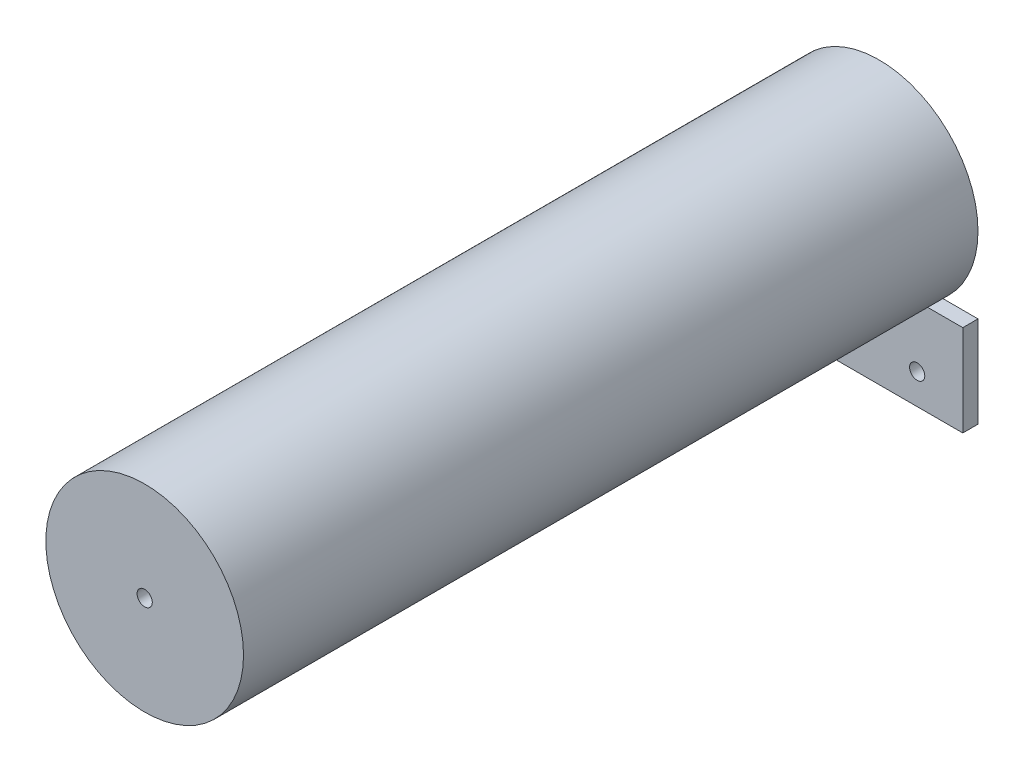
SolidWorks part; units mm, degrees
other "Asse"
other "PiastrinaAsse"
ref_plane "Piano frontale" through (0, 0, 0) normal (0, 0, 1) x (1, 0, 0)
ref_plane "Piano superiore" through (0, 0, 0) normal (0, 1, 0) x (1, 0, 0)
ref_plane "Piano destro" through (0, 0, 0) normal (1, 0, 0) x (0, 0, -1)
sketch "Sketch1" plane through (0, 0, 0) normal (0, 0, 1) x (1, 0, 0)
  circle A0 centre (0, 0) radius 65
  dimension "D1" = 130
extrude "ExtrudeAsse" add sketch "Sketch1" along normal blind 468 and the other way blind 15 contours A0 region at (0, 0, 0)
sketch "Sketch2" plane through (0, 0, 0) normal (0, 1, 0) x (1, 0, 0)
  line L0 (0, 0) -> (0, -468) construction
  line L1 (-65, -468) -> (65, -468) construction
  line L2 (65, -226.5) -> (-65, -226.5) construction
  line L3 (65, -468) -> (65, 15) construction
  line L4 (-65, 15) -> (-65, -468) construction
sketch "Sketch3" plane through (0, 0, 0) normal (1, 0, 0) x (0, 0, -1)
  line L0 (-468, 0) -> (0, 0) construction
  line L1 (-468, 65) -> (-468, -65) construction
  line L2 (-457.533, 10) -> (-194.4071, 10) construction
  line L4 (-335.5, 10) -> (-340.5, 12.8868)
  line L5 (-340.5, 12.8868) -> (-340.5, 10)
  line L7 (-227.7, 10) -> (-232.7, 12.8868)
  line L8 (-232.7, 12.8868) -> (-232.7, 0)
  line L9 (-340.5, 10) -> (-340.5, -65)
  line L10 (-468, -65) -> (15, -65) construction
  line L11 (-340.5, -65) -> (-335.5, -65)
  line L12 (-335.5, -65) -> (-335.5, 10)
  line L13 (-232.7, 0) -> (-232.7, -65)
  line L14 (-232.7, -65) -> (-227.7, -65)
  line L15 (-227.7, -65) -> (-227.7, 10)
  line L21 (-124.9, 10) -> (-124.9, 12.8868)
  line L22 (-124.9, 12.8868) -> (-119.9, 10)
  line L23 (-119.9, 10) -> (-119.9, -65)
  line L24 (-119.9, -65) -> (-124.9, -65)
  line L25 (-124.9, -65) -> (-124.9, 10)
  line L26 (-453, 40.9604) -> (-453, -28.8955) construction
  line L27 (-340.5, 12.8868) -> (-232.7, 12.8868) construction
  line L28 (-232.7, 12.8868) -> (-124.9, 12.8868) construction
  point P10 (-335.5, 9.1219)
  dimension "D1" = 10
  dimension "D2" = 5
  dimension "D3" = 124.9
  dimension "D4" = 30
  dimension "D5" = 5
  dimension "D6" = 5
  dimension "D7" = 107.8
  dimension "D8" = 30
  dimension "D10" = 15
  dimension "D11" = 30
revolve "Cut-Revolve1" cut sketch "Sketch3" angle 360 about L5 region at (0, -26.7738, 338.0157)
revolve "Cut-Revolve2" cut sketch "Sketch3<3>" angle 360 about L13 region at (0, -26.7738, 230.2157)
sketch "Sketch3<3>" plane through (0, 0, 0) normal (1, 0, 0) x (0, 0, -1) same geometry as "Sketch3"
sketch "Sketch4" plane through (0, 0, 0) normal (1, 0, 0) x (0, 0, -1)
  line L0 (-468, 0) -> (98.5282, 0) construction
  line L1 (-468, 65) -> (-468, -65) construction
  line L7 (-197.7711, -5) -> (-468, -5)
  line L8 (-468, -5) -> (-468, 0)
  line L9 (-468, 0) -> (-197.7711, 0)
  line L10 (-197.7711, -5) -> (-197.7711, 0) construction
  line L11 (-197.7711, -5) -> (-194.8844, 0)
  line L12 (-194.8844, 0) -> (-197.7711, 0)
  dimension "D1" = 30
  dimension "D2" = 5
  dimension "D3" = 270.2289
revolve "Cut-Revolve5" cut sketch "Sketch4" angle 360 about L0 region at (0, -2.4956, 332.1626)
sketch "Sketch5" plane through (0, 0, 0) normal (1, 0, 0) x (0, 0, -1)
  line L3 (15, -65) -> (15, 65) construction
  line L5 (15, -5) -> (15, 0)
  line L7 (-162.1132, 0) -> (-162.1132, -5) construction
  line L8 (15, 0) -> (-313.4256, 0) construction
  line L9 (15, 0) -> (-162.1132, 0)
  line L10 (-162.1132, -5) -> (15, -5)
  line L11 (-165, 0) -> (-162.1132, 0)
  line L12 (-162.1132, -5) -> (-165, 0)
  dimension "D1" = 180
  dimension "D2" = 30
  dimension "D3" = 5
revolve "Cut-Revolve6" cut sketch "Sketch5" angle 360 about L0
revolve "Cut-Revolve7" cut sketch "Sketch3<5>" angle 360 about L25
sketch "Sketch3<5>" plane through (0, 0, 0) normal (1, 0, 0) x (0, 0, -1) same geometry as "Sketch3"
ref_plane "Plane1" through (0, 0, 0) normal (0, 0, -1) x (-1, 0, 0)
sketch "Sketch6" plane through (0, 0, 0) normal (0, 0, -1) x (-1, 0, 0)
  line L1 (54.0154, -45) -> (-71.7504, -45)
  line L2 (54.0154, -45) -> (54.0154, -65)
  line L3 (54.0154, -65) -> (-71.7504, -65)
  line L4 (-71.7504, -45) -> (-71.7504, -65)
  dimension "D1" = 20
extrude "Cut-Extrude1" cut sketch "Sketch6" along normal blind 10
sketch "Sketch7" plane through (0, -45, 0) normal (0, -1, 0) x (1, 0, 0)
  line L0 (0, 0) -> (-70, 0)
  line L1 (-46.9042, 0) -> (46.9042, 0) construction
  line L2 (-70, 0) -> (-70, -10)
  line L3 (-70, -10) -> (0, -10)
  line L4 (0, -10) -> (0, 0)
  dimension "D1" = 70
extrude "ExtrPiastrina" add sketch "Sketch7" along normal blind 60 separate body
sketch "Sketch8" plane through (0, 0, -10) normal (0, 0, -1) x (-1, 0, 0)
  circle A0 centre (40, -85) radius 5
  point P5 (40.8526, -76.4463)
  dimension "D1" = 10
  dimension "D2" = 30
  dimension "D3" = 40
extrude "Foro" cut sketch "Sketch8" against normal up to surface (10 mm away) up to face at (-35, -75, 0)
mirror "Mirror1" about plane through (0, -105, -10) normal (-1, 0, 0) of bodies 115 113
